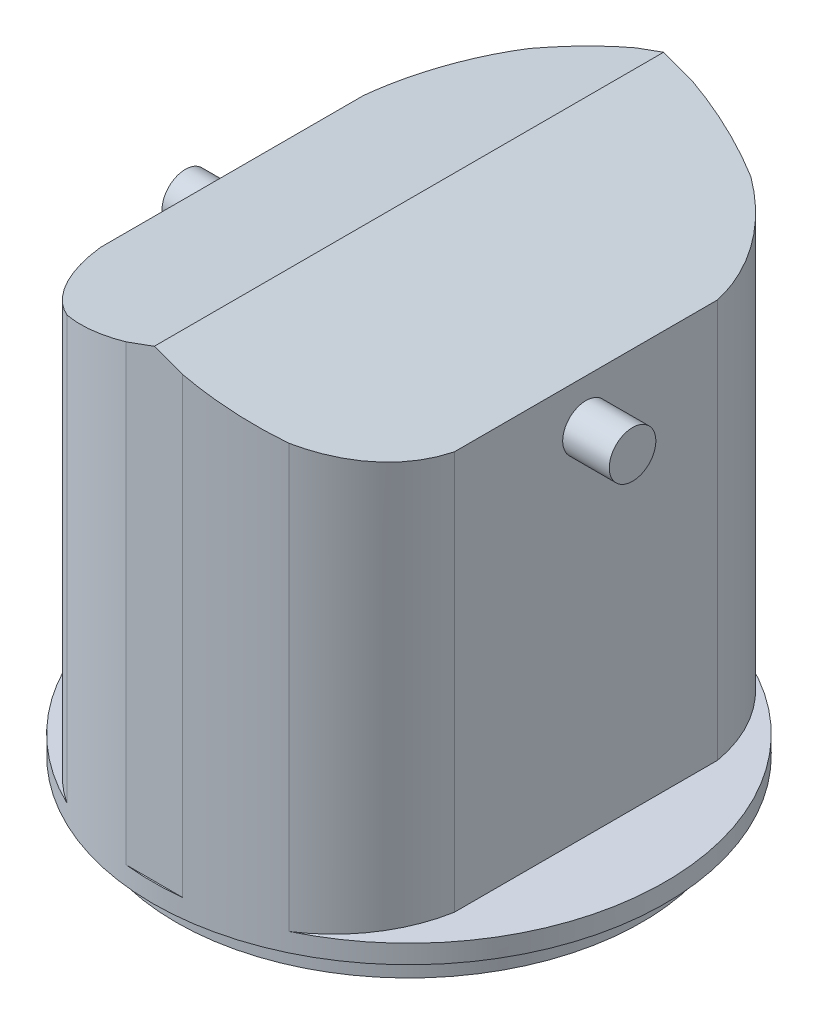
SolidWorks part; units mm, degrees
material "Galvanized Steel"
ref_plane "Front Plane" through (0, 0, 0) normal (0, 0, 1) x (1, 0, 0)
ref_plane "Top Plane" through (0, 0, 0) normal (0, 1, 0) x (1, 0, 0)
ref_plane "Right Plane" through (0, 0, 0) normal (1, 0, 0) x (0, 0, -1)
sketch "Sketch1" plane through (0, 0, 0) normal (0, 1, 0) x (1, 0, 0)
  circle A0 centre (0, 0) radius 27.5
  dimension "D1" = 55
extrude "Boss-Extrude1" add sketch "Sketch1" along normal blind 2
sketch "Sketch2" plane through (0, 0, 0) normal (0, -1, 0) x (1, 0, 0)
  circle A0 centre (0, 0) radius 25
  circle A1 centre (0, 0) radius 23
  dimension "D1" = 50
  dimension "D2" = 46
extrude "Boss-Extrude2" add sketch "Sketch2" along normal blind 3
sketch "Sketch3" plane through (0, 2, 0) normal (0, 1, 0) x (1, 0, 0)
  line L0 (19, 27.3347) -> (-19, -27.3347) construction
  line L5 (-19, 27.3347) -> (19, -27.3347) construction
  line L6 (0, 35.6081) -> (0, -36.7841) construction
  line L7 (-19, 27.3347) -> (-19, -14.1312)
  line L8 (19, 27.3347) -> (19, -14.1312)
  line L9 (3.2463, 27.3347) -> (-3.2463, 27.3347)
  line L10 (-11.5188, 0) -> (13.3229, 0) construction
  line L11 (3.2463, -27.3347) -> (-3.2463, -27.3347)
  arc A1 (-3.2463, 27.3347) -> (-19, 14.1312) centre (-3.2463, 11.3347) ccw
  arc A2 (3.2463, 27.3347) -> (19, 14.1312) centre (3.2463, 11.3347) cw
  arc A3 (3.2463, -27.3347) -> (19, -14.1312) centre (3.2463, -11.3347) ccw
  arc A4 (-3.2463, -27.3347) -> (-19, -14.1312) centre (-3.2463, -11.3347) cw
  point P8 (0, 27.3347)
  circle M2 centre (0, 0) radius 27.5
  dimension "D2" = 16
  dimension "D1" = 19
extrude "Boss-Extrude3" add sketch "Sketch3" along normal blind 50.8 contours A4 L11 A3 L8 A2 L9 A1 L7 M2 region at (0, 2, 0)
chamfer "Chamfer1" distance 8 angle 70 2 edges at (-19, 52.8, 0) (19, 52.8, 0) tangent propagation no first distance on face at (-19, 27.4, 0) first distance on face at (19, 27.4, 0)
sketch "Sketch4" plane through (-19, 0, 0) normal (-1, 0, 0) x (0, 0, 1)
  line L0 (-14.1312, 2) -> (14.1312, 2) construction
  circle A0 centre (0, 40) radius 2.5
  dimension "D1" = 38
  dimension "D2" = 5
extrude "Boss-Extrude4" add sketch "Sketch4" along normal blind 5
mirror "Mirror1" about plane through (0, 0, 0) normal (1, 0, 0) of "Boss-Extrude4"
